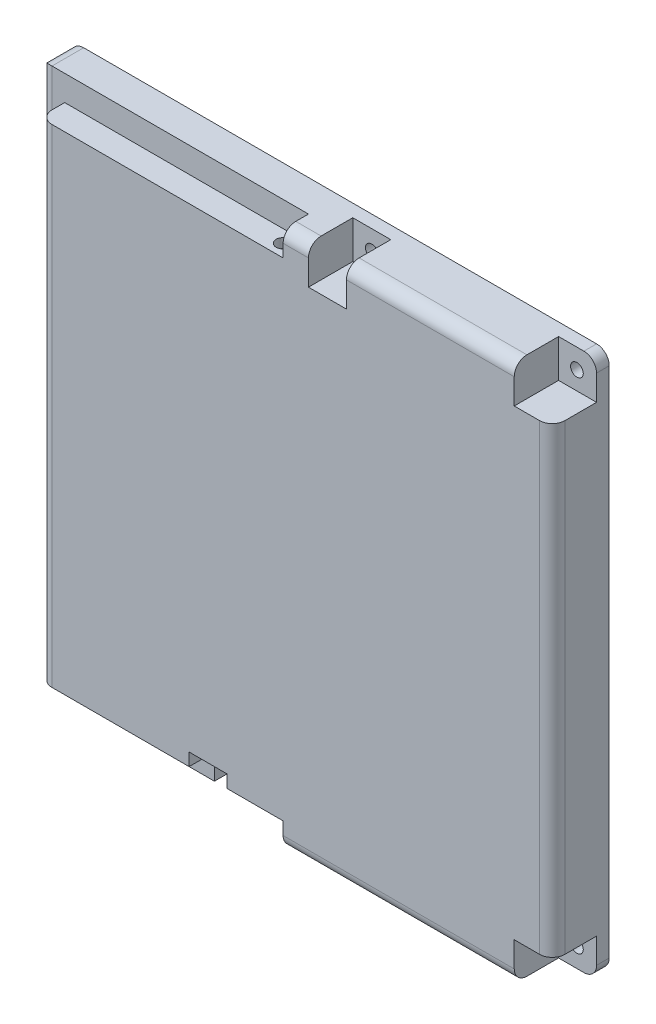
SolidWorks part; units mm, degrees
material "PLA"
ref_plane "前视基准面" through (0, 0, 0) normal (0, 0, 1) x (1, 0, 0)
ref_plane "上视基准面" through (0, 0, 0) normal (0, 1, 0) x (1, 0, 0)
ref_plane "右视基准面" through (0, 0, 0) normal (1, 0, 0) x (0, 0, -1)
sketch "草图1" plane through (0, 0, 0) normal (0, 0, 1) x (1, 0, 0)
  line L2 (70.4448, 16.0581) -> (70.4448, -68.9419)
  line L3 (70.4448, -68.9419) -> (155.4453, -68.9419)
  line L4 (70.4448, 16.0581) -> (155.4448, 16.0581)
  line L5 (155.4448, 16.0581) -> (155.4453, 16.0581)
  line L8 (155.4453, 16.0581) -> (155.4453, -68.9419)
  dimension "D1" = 85
  dimension "D2" = 85
extrude "凸台-拉伸1" add sketch "草图1" along normal blind 9
sketch "草图4" plane through (0, 0, 9) normal (0, 0, 1) x (1, 0, 0)
  line L1 (112.9451, 16.0581) -> (70.4448, 16.0581)
  line L6 (70.4448, 16.0581) -> (70.4448, -68.9419)
  line L10 (112.9451, -68.9419) -> (112.9451, 16.0581) construction
  line L11 (70.4448, -68.9419) -> (155.4453, -68.9419) construction
  line L13 (70.4448, -68.9419) -> (112.9451, -68.9419)
  line L14 (112.9451, -68.9419) -> (112.9451, -64.9419)
  line L15 (112.9451, -64.9419) -> (74.4448, -64.9419)
  line L16 (74.4448, -64.9419) -> (74.4448, 12.0581)
  line L17 (74.4448, 12.0581) -> (112.9451, 12.0581)
  line L18 (112.9451, 12.0581) -> (112.9451, 16.0581)
  dimension "D1" = 4
  dimension "D2" = 4
  dimension "D3" = 4
extrude "支架切除-拉伸2" cut sketch "草图4" against normal blind 4
sketch "草图7" plane through (0, 0, 9) normal (0, 0, 1) x (1, 0, 0)
  line L0 (155.4453, -26.4419) -> (112.9448, -26.4419) construction
  line L1 (155.4453, 16.0581) -> (149.4453, 16.0581)
  line L2 (155.4453, 16.0581) -> (155.4453, 10.0581)
  line L3 (155.4453, 10.0581) -> (149.4453, 10.0581)
  line L4 (149.4453, 16.0581) -> (149.4453, 10.0581)
  line L5 (155.4453, -68.9419) -> (155.4453, 16.0581) construction
  line L6 (149.4453, -68.9419) -> (149.4453, -62.9419)
  line L7 (155.4453, -62.9419) -> (149.4453, -62.9419)
  line L8 (155.4453, -68.9419) -> (155.4453, -62.9419)
  line L9 (155.4453, -68.9419) -> (149.4453, -68.9419)
  dimension "D1" = 6
  dimension "D2" = 6
extrude "顶螺丝切除-拉伸4" cut sketch "草图7" against normal blind 7
sketch "草图10" plane through (0, 0, 9) normal (0, 0, 1) x (1, 0, 0)
  line L0 (149.4453, 16.0581) -> (112.9451, 16.0581) construction
  line L1 (116.9448, 16.0581) -> (122.9448, 16.0581)
  line L2 (155.4453, -68.9419) -> (155.4453, -62.9419) construction
  line L3 (149.4453, -68.9419) -> (155.4453, -68.9419) construction
  line L4 (155.4453, -62.9419) -> (149.4453, -62.9419) construction
  line L5 (149.4453, -62.9419) -> (149.4453, -68.9419) construction
  line L6 (155.4453, 10.0581) -> (155.4453, 16.0581) construction
  line L7 (155.4453, 16.0581) -> (149.4453, 16.0581) construction
  line L8 (149.4453, 16.0581) -> (149.4453, 10.0581) construction
  line L9 (149.4453, 10.0581) -> (155.4453, 10.0581) construction
  line L10 (155.4453, -68.9419) -> (155.4453, -62.9419) construction
  line L11 (149.4453, -68.9419) -> (155.4453, -68.9419) construction
  line L12 (155.4453, -62.9419) -> (149.4453, -62.9419) construction
  line L13 (149.4453, -62.9419) -> (149.4453, -68.9419) construction
  line L14 (155.4453, 10.0581) -> (155.4453, 16.0581) construction
  line L15 (155.4453, 16.0581) -> (149.4453, 16.0581) construction
  line L16 (149.4453, 16.0581) -> (149.4453, 10.0581) construction
  line L17 (149.4453, 10.0581) -> (155.4453, 10.0581) construction
  line L18 (116.9448, 16.0581) -> (116.9448, 10.0581)
  line L19 (116.9448, 10.0581) -> (122.9448, 10.0581)
  line L20 (122.9448, 16.0581) -> (122.9448, 10.0581)
  line L22 (98.0948, -62.9419) -> (104.0948, -62.9419)
  line L23 (98.0948, -62.9419) -> (98.0948, -68.9419)
  line L24 (98.0948, -68.9419) -> (104.0948, -68.9419)
  line L25 (104.0948, -62.9419) -> (104.0948, -68.9419)
  line L28 (98.0948, -65.9419) -> (104.0948, -65.9419) construction
  line L30 (101.0948, -68.9419) -> (101.0948, -62.9419) construction
  line L31 (70.4448, -68.9419) -> (112.9451, -68.9419) construction
  circle A2 centre (101.0948, -65.8419) radius 0.825 construction
  circle A3 centre (119.9448, 12.9581) radius 0.825 construction
  dimension "D5" = 3
  dimension "D6" = 3
  dimension "D1" = 6
  dimension "D2" = 6
  dimension "D3" = 6
  dimension "D4" = 6
extrude "底螺丝切除-拉伸6" cut sketch "草图10" against normal blind 7
shell "抽壳1" thickness 1.5 removed face at (112.9451, -26.4419, 0)
sketch "草图5" plane through (0, 12.0581, 0) normal (0, 1, 0) x (1, 0, 0)
  line L0 (112.9451, -5) -> (70.4448, -5) construction
  line L2 (112.9451, -5) -> (112.9451, -9) construction
  circle A1 centre (110.9451, -7) radius 1 construction
  circle A2 centre (110.9451, -7) radius 1.1
  dimension "D1" = 2.2
  dimension "D2" = 2
  dimension "D3" = 2
extrude "切除-拉伸3" cut sketch "草图5" against normal blind 4
ref_plane "基准面1" through (0, -26.4419, 0) normal (0, 1, 0) x (1, 0, 0)
mirror "镜向1" about plane through (0, -26.4419, 0) normal (0, 1, 0) of "切除-拉伸3"
sketch "草图6" plane through (0, 0, 9) normal (0, 0, 1) x (1, 0, 0)
  circle A0 centre (152.3448, 12.9581) radius 1
  circle A1 centre (152.3448, -65.8419) radius 1
  dimension "D1" = 2
  dimension "D2" = 2
extrude "顶螺丝切除-拉伸5" cut sketch "草图6" against normal up to next from surface starting at face at (152.4453, 13.0581, 2)
fillet "圆角1" radius 2 10 edges at (131.1952, -68.9419, 9) (114.9449, 16.0581, 9) (70.4448, 16.0581, 2.5) (70.4448, -68.9419, 2.5) (155.4453, -68.9419, 1) (155.4453, 16.0581, 1) (155.4453, -26.4419, 9) (74.4448, -26.4419, 9) (70.4448, -26.4419, 5) (136.1951, 16.0581, 9)
sketch "草图12" plane through (0, 0, 2) normal (0, 0, 1) x (1, 0, 0)
  circle A0 centre (119.9448, 12.9581) radius 1
  circle A3 centre (101.0948, -65.8419) radius 1
  dimension "D1" = 2
extrude "底螺丝切除-拉伸7" cut sketch "草图12" against normal up to next
